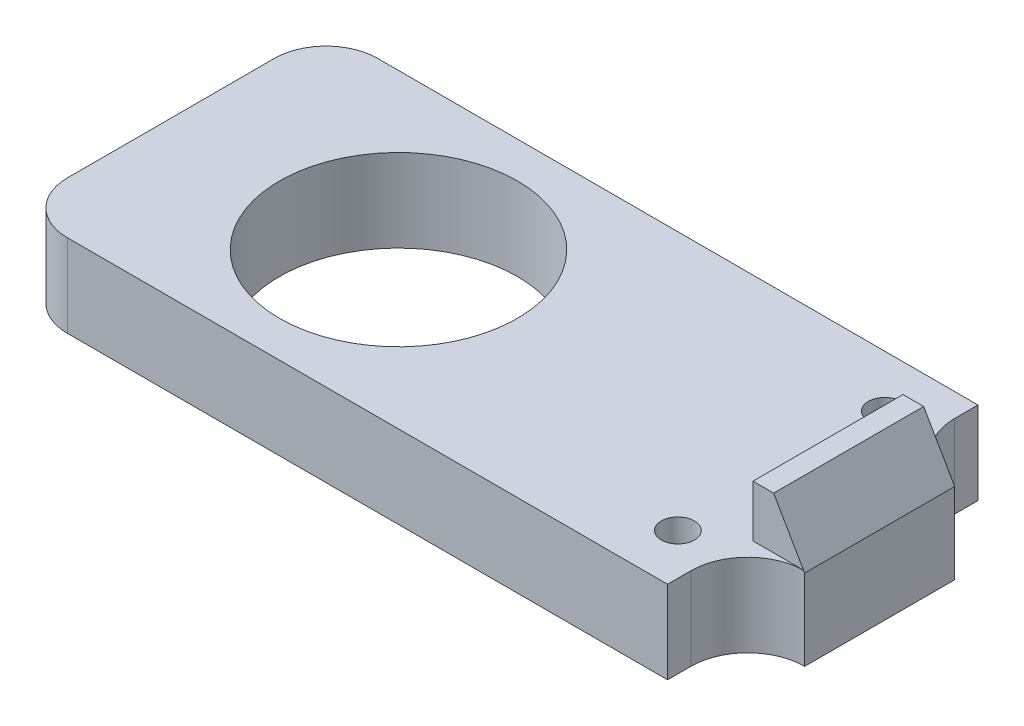
SolidWorks part; units mm, degrees
ref_plane "Front Plane" through (0, 0, 0) normal (0, 0, 1) x (1, 0, 0)
ref_plane "Top Plane" through (0, 0, 0) normal (0, 1, 0) x (1, 0, 0)
ref_plane "Right Plane" through (0, 0, 0) normal (1, 0, 0) x (0, 0, -1)
sketch "Sketch1" plane through (0, 0, 0) normal (0, 1, 0) x (1, 0, 0)
  line L1 (0, 0) -> (63, 0)
  line L2 (0, 0) -> (0, 30)
  line L3 (0, 30) -> (63, 30)
  line L4 (63, 0) -> (63, 30)
  circle A0 centre (22, 15) radius 11.5
  point P7 (0, 15)
  dimension "D3" = 23
  dimension "D4" = 22
  dimension "D1" = 63
  dimension "D2" = 30
extrude "Boss-Extrude1" add sketch "Sketch1" along normal blind 5
sketch "Sketch2" plane through (0, 5, 0) normal (0, 1, 0) x (1, 0, 0)
  line L0 (63, 0) -> (63, 30) construction
  line L1 (0, 0) -> (63, 0) construction
  line L2 (63, 30) -> (0, 30) construction
  circle A0 centre (59, 25) radius 1.6
  circle A1 centre (59, 5) radius 1.6
  dimension "D1" = 3.2
  dimension "D4" = 5
  dimension "D2" = 4
  dimension "D3" = 5
extrude "Cut-Extrude1" cut sketch "Sketch2" against normal through all
fillet "Fillet1" radius 5 2 edges at (0, 2.5, 0) (0, 2.5, -30)
sketch "Sketch3" plane through (63, 0, 0) normal (1, 0, 0) x (0, 0, -1)
  line L1 (7.75, 0) -> (22.25, 0)
  line L2 (7.75, 0) -> (7.75, 5)
  line L3 (7.75, 5) -> (22.25, 5)
  line L4 (22.25, 0) -> (22.25, 5)
  line L5 (0, 5) -> (30, 5) construction
  line L6 (0, 0) -> (30, 0) construction
  point P4 (15, 0)
  point P5 (0, 0)
  point P8 (15, 0)
  dimension "D1" = 14.5
extrude "Boss-Extrude2" add sketch "Sketch3" along normal blind 0.5 contours L2 L3 L4 L1
sketch "Sketch4" plane through (63.5, 0, 0) normal (1, 0, 0) x (0, 0, -1)
  line L0 (22.25, 0) -> (22.25, 5) construction
  line L1 (7.75, 0) -> (22.25, 0)
  line L2 (7.75, 0) -> (7.75, 10)
  line L3 (7.75, 10) -> (22.25, 10)
  line L4 (22.25, 0) -> (22.25, 10)
  dimension "D1" = 10
extrude "Boss-Extrude3" add sketch "Sketch4" along normal blind 5
fillet "Fillet2" radius 5.5 2 edges at (63, 2.5, -7.75) (63, 2.5, -22.25)
sketch "Sketch5" plane through (68.5, 0, 0) normal (1, 0, 0) x (0, 0, -1)
  line L0 (7.75, 10) -> (7.75, 0) construction
  line L1 (4.5413, 5) -> (7.75, 5)
  line L2 (4.5413, 5) -> (4.5413, 10)
  line L3 (4.5413, 10) -> (7.75, 10)
  line L4 (7.75, 5) -> (7.75, 10)
  line L5 (22.25, 10) -> (25.4587, 10)
  line L6 (22.25, 10) -> (22.25, 5)
  line L7 (22.25, 5) -> (25.4587, 5)
  line L8 (25.4587, 10) -> (25.4587, 5)
  line L9 (22.25, 0) -> (22.25, 10) construction
extrude "Cut-Extrude2" cut sketch "Sketch5" against normal through all
chamfer "Chamfer1" distance 3 angle 60 1 edges at (68.5, 10, -15) first distance on face at (66, 10, -15)
sketch "Sketch6" plane through (0, 0, 0) normal (0, -1, 0) x (1, 0, 0)
  line L12 (63, 0) -> (5, 0)
  line L13 (0, -5) -> (0, -25)
  line L14 (5, -30) -> (63, -30)
  line L15 (63, -30) -> (63, -27.75)
  line L16 (68.5, -22.25) -> (68.5, -7.75)
  line L17 (63, -2.25) -> (63, 0)
  line L18 (63, 0) -> (5, 0)
  line L19 (0, -5) -> (0, -25)
  line L20 (5, -30) -> (63, -30)
  line L21 (63, -30) -> (63, -27.75)
  line L22 (68.5, -22.25) -> (68.5, -7.75)
  line L23 (63, -2.25) -> (63, 0)
  arc A8 (5, 0) -> (0, -5) centre (5, -5) ccw
  arc A9 (0, -25) -> (5, -30) centre (5, -25) ccw
  arc A10 (68.5, -22.25) -> (63, -27.75) centre (68.5, -27.75) ccw
  arc A11 (63, -2.25) -> (68.5, -7.75) centre (68.5, -2.25) ccw
  arc A12 (5, 0) -> (0, -5) centre (5, -5) ccw
  arc A13 (0, -25) -> (5, -30) centre (5, -25) ccw
  arc A14 (68.5, -22.25) -> (63, -27.75) centre (68.5, -27.75) ccw
  arc A15 (63, -2.25) -> (68.5, -7.75) centre (68.5, -2.25) ccw
  circle M11 centre (59, -25) radius 1.6
  circle M12 centre (59, -5) radius 1.6
  line M13 (63, 0) -> (5, 0)
  arc M14 (5, 0) -> (0, -5) centre (5, -5) ccw
  line M15 (0, -5) -> (0, -25)
  arc M16 (0, -25) -> (5, -30) centre (5, -25) ccw
  line M17 (5, -30) -> (63, -30)
  line M18 (63, -30) -> (63, -27.75)
  arc M19 (63, -27.75) -> (68.5, -22.25) centre (68.5, -27.75) cw
  line M20 (68.5, -22.25) -> (68.5, -7.75)
  arc M21 (68.5, -7.75) -> (63, -2.25) centre (68.5, -2.25) cw
  line M22 (63, -2.25) -> (63, 0)
  circle M23 centre (22, -15) radius 11.5
  dimension "D1" = 0
extrude "Boss-Extrude4" add sketch "Sketch6" along normal blind 3 contours M22 M13 M14 M15 M16 M17 M18 M19 M20 M21 M12 M23 M11 region at (36.0357, 0, -15)
